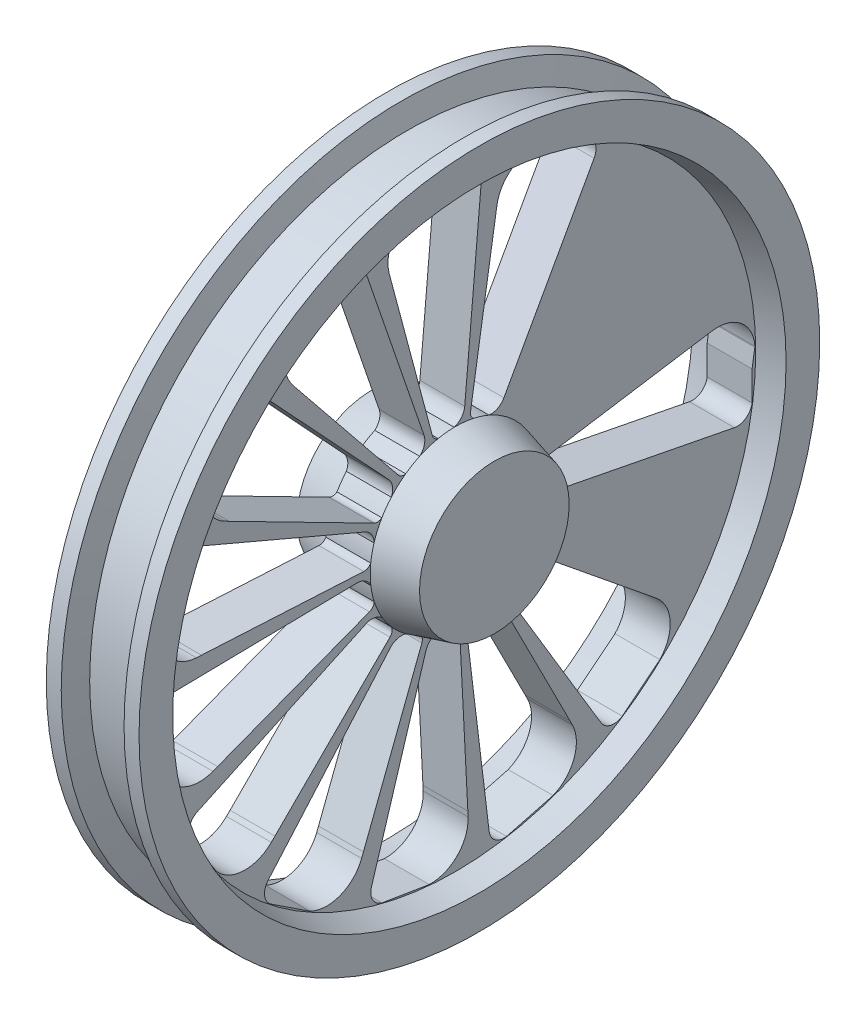
SolidWorks part; units mm, degrees
material "Alliage 1060"
ref_plane "Plan de face" through (0, 0, 0) normal (0, 0, 1) x (1, 0, 0)
ref_plane "Plan de dessus" through (0, 0, 0) normal (0, 1, 0) x (1, 0, 0)
ref_plane "Plan de droite" through (0, 0, 0) normal (1, 0, 0) x (0, 0, -1)
sketch "Esquisse1" plane through (0, 0, 0) normal (0, 0, 1) x (1, 0, 0)
  line L0 (51.1425, 233.8946) -> (71.1425, 233.8946)
  line L1 (71.1425, 233.8946) -> (79.181, 203.8946)
  line L2 (79.181, 203.8946) -> (147.1041, 203.8946)
  line L3 (147.1041, 203.8946) -> (155.1425, 233.8946)
  line L4 (155.1425, 233.8946) -> (175.1425, 233.8946)
  line L5 (175.1425, 233.8946) -> (175.1425, 188.8946)
  line L6 (175.1425, 188.8946) -> (143.1425, 180.3202)
  line L7 (143.1425, 180.3202) -> (143.1425, -107.1721)
  line L8 (143.1425, -107.1721) -> (195.1425, -121.1054)
  line L10 (195.1425, -121.1054) -> (195.1425, -221.1054)
  line L11 (195.1425, -221.1054) -> (31.1425, -221.1054)
  line L12 (31.1425, -221.1054) -> (31.1425, -121.1054)
  line L13 (31.1425, -121.1054) -> (83.1425, -107.1721)
  line L14 (83.1425, -107.1721) -> (83.1425, 180.3202)
  line L15 (83.1425, 180.3202) -> (51.1425, 188.8946)
  line L16 (51.1425, 188.8946) -> (51.1425, 233.8946)
  line L17 (31.1425, -121.1054) -> (195.1425, -121.1054) construction
  line L18 (71.1425, 233.8946) -> (71.1425, 159.3597) construction
  line L19 (155.1425, 233.8946) -> (155.1425, 155.5185)
  line L20 (51.1425, 188.8946) -> (148.536, 188.8946) construction
  line L21 (51.1425, 233.8946) -> (175.1425, 233.8946) construction
  point P23 (79.181, 203.8946)
  dimension "D1" = 60
  dimension "D2" = 100
  dimension "D3" = 15
  dimension "D4" = 455
  dimension "D5" = 15
  dimension "D6" = 15
  dimension "D7" = 15
  dimension "D8" = 164
  dimension "D9" = 45
  dimension "D10" = 45
  dimension "D11" = 30
  dimension "D12" = 20
  dimension "D13" = 124
  dimension "D14" = 15
  dimension "D15" = 15
revolve "Révolution1" add sketch "Esquisse1" angle 360 about L11 region at (111.8541, -45.1087, 0) region at (164.9552, 210.0297, 0)
sketch "Esquisse2" plane through (83.1425, 0, 0) normal (-1, 0, 0) x (0, 0, 1)
  line L0 (-117.8578, 162.629) -> (-117.8406, 162.6342)
  line L6 (-100, -221.1054) -> (100, -221.1054)
  line L7 (0, -321.1054) -> (0, -121.1054)
  line L8 (30.849, -102.3063) -> (86.824, 107.6673)
  line L9 (42.041, -96.1248) -> (122.568, 138.7163)
  line L10 (86.824, 107.6673) -> (88.551, 114.2069)
  line L11 (48.6658, 176.253) -> (48.1006, 176.35)
  line L12 (148.948, 150.7852) -> (173.1933, 141.0363)
  line L13 (52.7837, -120.8645) -> (53.3216, -121.1054)
  line L14 (19.1866, -109.5284) -> (9.6457, -107.5811)
  line L15 (19.1866, -109.5284) -> (32.7092, -111.9683)
  line L16 (32.7092, -111.9683) -> (52.7837, -120.8645)
  line L17 (48.1006, 176.35) -> (75.4732, 173.1614)
  line L18 (75.4732, 173.1614) -> (124.9878, 160.3662)
  line L19 (124.9878, 160.3662) -> (148.948, 150.7852)
  line L20 (76.5019, -125.1244) -> (213.0416, 43.9289)
  line L21 (89.2406, -124.0295) -> (258.3241, 57.7551)
  line L22 (213.0416, 43.9289) -> (217.2791, 49.2007)
  line L23 (62.9103, -126.9787) -> (74.2715, -134.7077)
  line L24 (74.2715, -134.7077) -> (88.9919, -150.9998)
  line L25 (205.6018, 122.4239) -> (229.3109, 108.3775)
  line L26 (229.3109, 108.3775) -> (269.3405, 76.5491)
  line L27 (269.3405, 76.5491) -> (287.3323, 58.0509)
  line L28 (108.927, -164.5385) -> (302.4224, -65.6363)
  line L29 (121.0096, -168.7196) -> (349.4136, -71.4235)
  line L30 (302.4224, -65.6363) -> (308.4378, -62.5439)
  line L31 (95.7562, -160.7043) -> (102.9915, -172.3861)
  line L32 (102.9915, -172.3861) -> (109.8127, -193.257)
  line L33 (327.5525, 9.0984) -> (343.4988, -13.3769)
  line L34 (343.4988, -13.3769) -> (367.1218, -58.7351)
  line L35 (367.1218, -58.7351) -> (376.0342, -82.952)
  line L36 (122.5176, -213.7336) -> (339.5116, -202.0836)
  line L37 (131.855, -222.4676) -> (380.0864, -226.4835)
  line L38 (339.5116, -202.0836) -> (346.2647, -201.7052)
  line L39 (112.045, -204.8738) -> (113.9033, -218.4885)
  line L40 (113.9033, -218.4885) -> (111.6459, -240.3295)
  line L41 (392.8664, -144.0313) -> (398.2925, -171.0495)
  line L42 (398.2925, -171.0495) -> (401.4244, -222.0946)
  line L43 (401.4244, -222.0946) -> (399.7164, -247.8428)
  line L44 (114.9238, -264.2033) -> (317.8961, -341.8199)
  line L45 (119.9015, -275.9802) -> (345.0387, -380.6136)
  line L46 (317.8961, -341.8199) -> (324.2193, -344.221)
  line L47 (108.9602, -251.8499) -> (105.1202, -265.0434)
  line L48 (105.1202, -265.0434) -> (94.1744, -284.078)
  line L49 (390.2502, -310.4879) -> (384.2179, -337.3773)
  line L50 (384.2179, -337.3773) -> (366.3171, -385.2831)
  line L51 (366.3171, -385.2831) -> (354.284, -408.1106)
  line L52 (87.4586, -307.221) -> (241.3136, -460.6836)
  line L53 (87.2159, -320.0043) -> (250.3307, -507.1633)
  line L54 (241.3136, -460.6836) -> (246.1134, -465.449)
  line L55 (87.0352, -293.51) -> (78.1609, -304.001)
  line L56 (78.1609, -304.001) -> (60.4194, -316.9379)
  line L57 (320.1561, -461.4895) -> (303.7085, -483.6005)
  line L58 (303.7085, -483.6005) -> (267.8702, -520.0838)
  line L59 (267.8702, -520.0838) -> (247.5927, -536.0434)
  line L60 (44.871, -335.3485) -> (123.0057, -538.122)
  line L61 (39.4499, -346.928) -> (112.3383, -584.2509)
  line L62 (123.0057, -538.122) -> (125.4523, -544.4277)
  line L63 (50.061, -322.6507) -> (37.6869, -328.6252)
  line L64 (37.6869, -328.6252) -> (16.2173, -333.2275)
  line L65 (194.7042, -570.9264) -> (170.6851, -584.436)
  line L66 (170.6851, -584.436) -> (123.1062, -603.1884)
  line L67 (123.1062, -603.1884) -> (98.0904, -609.5206)
  line L68 (-5.4751, -343.7224) -> (-16.571, -560.7454)
  line L69 (-15.1374, -352.0958) -> (-45.0785, -598.5475)
  line L70 (-16.571, -560.7454) -> (-16.9006, -567.5011)
  line L71 (4.4308, -334.2333) -> (-9.3036, -334.6583)
  line L72 (-9.3036, -334.6583) -> (-30.7889, -330.1302)
  line L73 (35.5861, -619.8761) -> (8.1488, -622.4483)
  line L74 (8.1488, -622.4483) -> (-42.9441, -620.2274)
  line L75 (-42.9441, -620.2274) -> (-68.3727, -615.8373)
  line L76 (-54.8746, -330.8946) -> (-153.2824, -524.642)
  line L77 (-67.1072, -334.6141) -> (-194.7007, -547.5808)
  line L78 (-153.2824, -524.642) -> (-156.3313, -530.6795)
  line L79 (-41.9655, -326.2551) -> (-54.6854, -321.057)
  line L80 (-54.6854, -321.057) -> (-72.4715, -308.1815)
  line L81 (-129.6851, -599.8748) -> (-155.7966, -591.0648)
  line L82 (-155.7966, -591.0648) -> (-201.5689, -568.2545)
  line L83 (-201.5689, -568.2545) -> (-223.0135, -553.9013)
  line L84 (-94.7857, -299.0834) -> (-263.4899, -436.0543)
  line L85 (-107.4737, -297.5058) -> (-310.6575, -440.1636)
  line L86 (-263.4899, -436.0543) -> (-268.7309, -440.3298)
  line L87 (-81.1056, -300.0955) -> (-90.6115, -290.1732)
  line L88 (-90.6115, -290.1732) -> (-101.623, -271.1766)
  line L89 (-272.5326, -514.3807) -> (-292.8033, -495.712)
  line L90 (-292.8033, -495.712) -> (-325.3406, -456.2565)
  line L91 (-325.3406, -456.2565) -> (-339.0932, -434.4218)
  line L92 (-118.3076, -253.789) -> (-328.1376, -310.3)
  line L93 (-129.2569, -247.1872) -> (-372.8987, -294.8692)
  line L94 (-328.1376, -310.3) -> (-334.6644, -312.0741)
  line L95 (-106.2218, -260.2778) -> (-110.8702, -247.347)
  line L96 (-110.8702, -247.347) -> (-113.203, -225.5139)
  line L97 (-368.2568, -378.1768) -> (-379.1817, -352.8771)
  line L98 (-379.1817, -352.8771) -> (-392.858, -303.5986)
  line L99 (-392.858, -303.5986) -> (-396.5407, -278.058)
  line L100 (-121.3729, -202.8433) -> (-336.0473, -169.1231)
  line L101 (-128.6905, -192.3587) -> (-370.6624, -136.8204)
  line L102 (-336.0473, -169.1231) -> (-342.7315, -168.0892)
  line L103 (-112.9713, -213.6868) -> (-111.9583, -199.9833)
  line L104 (-111.9583, -199.9833) -> (-105.2092, -179.0889)
  line L105 (-400.306, -214.8137) -> (-399.9961, -187.2578)
  line L106 (-399.9961, -187.2578) -> (-392.4466, -136.677)
  line L107 (-392.4466, -136.677) -> (-385.4226, -111.8466)
  line L108 (-103.4518, -155.0553) -> (-285.8514, -36.9345)
  line L109 (-105.8723, -142.5009) -> (-304.3352, 6.6547)
  line L110 (-285.8514, -36.9345) -> (-291.5372, -33.2712)
  line L111 (-100.187, -168.3786) -> (-93.6879, -156.2718)
  line L112 (-93.6879, -156.2718) -> (-79.0238, -139.929)
  line L113 (-363.1386, -52.5386) -> (-351.6475, -27.491)
  line L114 (-351.6475, -27.491) -> (-324.1777, 15.6462)
  line L115 (-324.1777, 15.6462) -> (-307.6615, 35.473)
  line L116 (-67.643, -118.688) -> (-186.2292, 63.4093)
  line L117 (-64.7478, -106.2345) -> (-185.3856, 110.7481)
  line L118 (-186.2292, 63.4093) -> (-189.9334, 69.0685)
  line L119 (-70.0795, -132.1874) -> (-59.2179, -123.7707)
  line L120 (-59.2179, -123.7707) -> (-39.1744, -114.8052)
  line L121 (-263.1813, 80.5899) -> (-242.4959, 98.7981)
  line L122 (-242.4959, 98.7981) -> (-199.8555, 127.0329)
  line L123 (-199.8555, 127.0329) -> (-176.7029, 138.4279)
  line L124 (-20.138, -100.0296) -> (-54.4063, 114.558)
  line L125 (-12.4278, -89.8303) -> (-34.3812, 157.461)
  line L126 (-54.4063, 114.558) -> (-55.4884, 121.2345)
  line L127 (-27.8546, -111.3708) -> (-14.5087, -108.0996)
  line L128 (-14.5087, -108.0996) -> (7.4486, -108.0617)
  line L129 (-117.7176, 161.5524) -> (-91.4146, 169.773)
  line L130 (-91.4146, 169.773) -> (-40.9765, 178.2233)
  line L131 (-40.9765, 178.2233) -> (-15.1908, 179.2161)
  line L132 (-176.7029, 138.4279) -> (-117.8406, 162.6342)
  line L133 (48.6658, 176.253) -> (-15.1908, 179.2161)
  line L134 (173.1933, 141.0363) -> (206.0786, 122.1054)
  line L135 (287.3323, 58.0509) -> (327.5525, 9.0984)
  line L136 (376.0342, -82.952) -> (392.8664, -144.0313)
  line L137 (399.7164, -247.8428) -> (390.2502, -310.4879)
  line L138 (324.2193, -457.8001) -> (327.2503, -453.5915)
  line L139 (-131.1673, -599.3747) -> (-68.3727, -615.8373)
  line L140 (-273.9608, -513.0655) -> (-223.0135, -553.9013)
  line L141 (-368.2568, -378.1768) -> (-339.0932, -434.4218)
  line L142 (-400.2686, -214.2415) -> (-396.5407, -278.058)
  line L143 (-363.1386, -52.5386) -> (-385.4226, -111.8466)
  line L144 (-263.1813, 80.5899) -> (-307.6615, 35.473)
  line L145 (-117.7176, 161.5524) -> (-176.7029, 138.4279)
  line L146 (48.6658, 176.253) -> (-15.1908, 179.2161)
  line L147 (287.4774, 57.8744) -> (327.8586, 8.6135)
  line L148 (376.0342, -82.952) -> (392.9488, -144.5989)
  line L149 (399.7164, -247.8428) -> (390.0946, -311.0399)
  line L150 (354.284, -408.1106) -> (319.7895, -461.9304)
  line L151 (247.5927, -536.0434) -> (194.1899, -571.1801)
  line L152 (35.5861, -619.8761) -> (98.0904, -609.5206)
  line L153 (-129.6851, -599.8748) -> (-70.0795, -615.3899)
  line L154 (-272.5326, -514.3807) -> (-223.0135, -553.9013)
  line L155 (-366.9932, -380.6136) -> (-339.0932, -434.4218)
  line L156 (35.5861, -619.8761) -> (98.0904, -609.5206)
  line L157 (-368.2568, -378.1768) -> (-339.0932, -434.4218)
  line L158 (-363.1386, -52.5386) -> (-385.4226, -111.8466)
  line L159 (-263.1813, 80.5899) -> (-307.6615, 35.473)
  line L160 (-117.1618, 161.6937) -> (-176.7029, 138.4279)
  line L161 (35.0131, -619.8987) -> (98.0904, -609.5206)
  line L162 (-106.2218, -260.2778) -> (-101.623, -271.1766)
  line L163 (-100.187, -168.3786) -> (-105.2092, -179.0889)
  line L164 (-70.0795, -132.1874) -> (-79.0238, -139.929)
  line L165 (-363.1386, -52.5386) -> (-385.4226, -111.8466)
  line L166 (-100.187, -168.2673) -> (-103.1615, -172.9523)
  line L167 (-103.1615, -172.9523) -> (-105.2092, -179.0889)
  line L168 (-363.1386, -52.5386) -> (-372.8987, -82.4119)
  line L169 (-372.8987, -82.4119) -> (-385.5567, -112.3204)
  line L170 (-307.6615, 35.473) -> (-282.8766, 62.4734)
  line L171 (-282.8766, 62.4734) -> (-263.1813, 80.5899)
  line L172 (-282.8766, 62.0557) -> (-282.8766, 62.4734)
  line L173 (-282.8766, 62.4734) -> (-307.6615, 35.473)
  line L174 (-282.8766, 62.0557) -> (-307.6615, 35.473)
  line L175 (-307.6615, 35.473) -> (-292.0889, 53.417)
  line L176 (-292.0889, 53.417) -> (-282.8766, 61.8307)
  line L177 (-282.8766, 61.8307) -> (-282.8766, 62.0557)
  line L178 (-106.2218, -260.2778) -> (-101.5238, -271.3479)
  line L179 (-106.2218, -260.2778) -> (-106.2218, -265.0434)
  line L180 (-106.2218, -265.0434) -> (-101.3705, -271.6122)
  line L181 (-338.8163, -434.8616) -> (-348.7383, -402.6142)
  line L182 (-348.7383, -402.6142) -> (-368.2568, -378.1768)
  line L183 (-396.5407, -278.058) -> (-396.5407, -238.7218)
  line L184 (-396.5407, -238.7218) -> (-400.306, -214.8137)
  line L185 (-112.9713, -213.6868) -> (-114.4986, -218.4885)
  line L186 (-114.4986, -218.4885) -> (-113.203, -225.5139)
  line L187 (-100.187, -168.3786) -> (-105.5618, -176.6782)
  line L188 (-105.5618, -176.6782) -> (-105.2939, -179.342)
  line L189 (-307.6615, 35.473) -> (-266.5954, 74.2264)
  line L190 (-266.5954, 74.2264) -> (-263.4168, 80.351)
  line L191 (-70.0795, -132.1874) -> (-78.7587, -136.8204)
  line L192 (-78.7587, -136.8204) -> (-79.3723, -139.6632)
  circle A0 centre (0, -221.1054) radius 401.4256 construction
  circle A1 centre (0, -221.1054) radius 113.9334 construction
  circle A6 centre (0, -221.1054) radius 100 construction
  arc A7 (48.6658, 176.253) -> (88.551, 114.2069) centre (40.2083, 126.9734) cw
  arc A8 (148.948, 150.7852) -> (122.568, 138.7163) centre (141.4867, 132.2291) ccw
  arc A9 (52.7837, -120.8645) -> (42.041, -96.1248) centre (60.9597, -102.612) cw
  arc A10 (30.849, -102.3063) -> (19.1866, -109.5284) centre (21.1864, -99.7304) cw
  arc A11 (88.9919, -150.9998) -> (89.2406, -124.0295) centre (103.8851, -137.6508) cw
  arc A12 (76.5019, -125.1244) -> (62.9103, -126.9787) centre (68.7224, -118.8411) cw
  arc A13 (206.0786, 122.1054) -> (217.2791, 49.2007) centre (178.3086, 80.5262) cw
  arc A14 (287.3323, 58.0509) -> (258.3241, 57.7551) centre (272.9686, 44.1339) ccw
  arc A15 (109.8127, -193.257) -> (121.0096, -168.7196) centre (128.8478, -187.1197) cw
  arc A16 (108.927, -164.5385) -> (95.7562, -160.7043) centre (104.3757, -155.6343) cw
  arc A17 (327.8586, 8.6135) -> (308.4378, -62.5439) centre (285.5776, -18.0758) cw
  arc A18 (376.0342, -82.952) -> (349.4136, -71.4235) centre (357.2518, -89.8236) ccw
  arc A19 (111.6459, -240.3295) -> (131.855, -222.4676) centre (131.5315, -242.465) cw
  arc A20 (122.5176, -213.7336) -> (112.045, -204.8738) centre (121.9815, -203.748) cw
  arc A21 (392.9488, -144.5989) -> (346.2647, -201.7052) centre (343.4677, -151.7835) cw
  arc A22 (399.7164, -247.8428) -> (380.0864, -226.4835) centre (379.7628, -246.4809) ccw
  arc A23 (94.1744, -284.078) -> (119.9015, -275.9802) centre (111.4723, -294.1171) cw
  arc A24 (114.9238, -264.2033) -> (108.9602, -251.8499) centre (118.4955, -254.8629) cw
  arc A25 (390.0946, -311.0399) -> (324.2193, -344.221) centre (341.9691, -297.4776) cw
  arc A26 (354.284, -408.1106) -> (345.0387, -380.6136) centre (336.6095, -398.7505) ccw
  arc A27 (60.4194, -316.9379) -> (87.2159, -320.0043) centre (72.1385, -333.1448) cw
  arc A28 (87.4586, -307.221) -> (87.0352, -293.51) centre (94.5206, -300.1409) cw
  arc A29 (319.7895, -461.9304) -> (246.1134, -465.449) centre (281.341, -429.9663) cw
  arc A30 (247.5927, -536.0434) -> (250.3307, -507.1633) centre (235.2533, -520.3037) ccw
  arc A31 (16.2173, -333.2275) -> (39.4499, -346.928) centre (20.3313, -352.7998) cw
  arc A32 (44.871, -335.3485) -> (50.061, -322.6507) centre (54.2022, -331.7529) cw
  arc A33 (194.1899, -571.1801) -> (125.4523, -544.4277) centre (172.0664, -526.341) cw
  arc A34 (98.0904, -609.5206) -> (112.3383, -584.2509) centre (93.2197, -590.1228) ccw
  arc A35 (-30.7889, -330.1302) -> (-15.1374, -352.0958) centre (-34.9914, -349.6837) cw
  arc A36 (-5.4751, -343.7224) -> (4.4308, -334.2333) centre (4.5118, -344.233) cw
  arc A37 (35.0131, -619.8987) -> (-16.9006, -567.5011) centre (33.04, -569.9377) cw
  arc A38 (-68.3727, -615.8373) -> (-45.0785, -598.5475) centre (-64.9325, -596.1354) ccw
  arc A39 (-72.4715, -308.1815) -> (-67.1072, -334.6141) centre (-84.2637, -324.3353) cw
  arc A40 (-54.8746, -330.8946) -> (-41.9655, -326.2551) centre (-45.9587, -335.4232) cw
  arc A41 (-130.2178, -599.6624) -> (-156.3313, -530.6795) centre (-111.6993, -553.2181) cw
  arc A42 (-223.0135, -553.9013) -> (-194.7007, -547.5808) centre (-211.8572, -537.3019) ccw
  arc A43 (-101.623, -271.1766) -> (-107.4737, -297.5058) centre (-118.9661, -281.1374) cw
  arc A44 (-94.7857, -299.0834) -> (-81.1056, -300.0955) centre (-88.4826, -306.8468) cw
  arc A45 (-272.9329, -513.9701) -> (-268.7309, -440.3298) centre (-237.1248, -479.0733) cw
  arc A46 (-339.0932, -434.4218) -> (-310.6575, -440.1636) centre (-322.1499, -423.7952) ccw
  arc A47 (-113.203, -225.5139) -> (-129.2569, -247.1872) centre (-133.0982, -227.5595) cw
  arc A48 (-118.3076, -253.789) -> (-106.2218, -260.2778) centre (-115.7071, -263.4449) cw
  arc A49 (-368.4553, -377.6388) -> (-334.6644, -312.0741) centre (-321.5493, -360.3234) cw
  arc A50 (-396.5407, -278.058) -> (-372.8987, -294.8692) centre (-376.74, -275.2416) ccw
  arc A51 (-105.2092, -179.0889) -> (-128.6905, -192.3587) centre (-124.2163, -172.8656) cw
  arc A52 (-121.3729, -202.8433) -> (-112.9713, -213.6868) centre (-122.9247, -212.7222) cw
  arc A53 (-400.2686, -214.2415) -> (-342.7315, -168.0892) centre (-350.375, -217.5015) cw
  arc A54 (-385.4226, -111.8466) -> (-370.6624, -136.8204) centre (-366.1883, -117.3273) ccw
  arc A55 (-79.0238, -139.929) -> (-105.8723, -142.5009) centre (-93.8564, -126.5128) cw
  arc A56 (-103.4518, -155.0553) -> (-100.187, -168.3786) centre (-108.8875, -163.449) cw
  arc A57 (-362.8717, -52.031) -> (-291.5372, -33.2712) centre (-318.6176, -75.3027) cw
  arc A58 (-307.6615, 35.473) -> (-304.3352, 6.6547) centre (-292.3193, 22.6428) ccw
  arc A59 (-39.1744, -114.8052) -> (-64.7478, -106.2345) centre (-47.2678, -96.516) cw
  arc A60 (-67.643, -118.688) -> (-70.0795, -132.1874) centre (-76.0227, -124.1451) cw
  arc A61 (-262.731, 80.945) -> (-189.9334, 69.0685) centre (-231.7684, 41.6854) cw
  arc A62 (-176.7029, 138.4279) -> (-185.3856, 110.7481) centre (-167.9056, 120.4666) ccw
  arc A63 (7.4486, -108.0617) -> (-12.4278, -89.8303) centre (7.4938, -88.0617) cw
  arc A64 (-20.138, -100.0296) -> (-27.8546, -111.3708) centre (-30.0129, -101.6065) cw
  arc A65 (-117.1618, 161.6937) -> (-55.4884, 121.2345) centre (-104.8443, 113.2346) cw
  arc A66 (-15.1908, 179.2161) -> (-34.3812, 157.461) centre (-14.4596, 159.2295) ccw
  circle A67 centre (0, -221.1054) radius 455 construction
  circle A68 centre (0, -221.1054) radius 401.4256
  circle A70 centre (0, -221.1054) radius 113.9334
  circle A71 centre (0, -221.1054) radius 113.9334
  point P10 (102.4967, 167.0144)
  point P11 (12.9028, 180.1128)
  point P12 (-36.3379, 178.6721)
  point P19 (-3.0907, -107.214)
  point P27 (0, -221.1054)
  point P279 (0, -221.1054)
  circle M12 centre (0, -221.1054) radius 113.9334
  dimension "D1" = 50
  dimension "D2" = 20
  dimension "D3" = 20
  dimension "D4" = 10
  dimension "D5" = 4
  dimension "D7" = 0
  dimension "D6" = 15
extrude "Enlèv. mat.-Extru.2" cut sketch "Esquisse2" against normal through all contours A53 L142 L99 A50 L93 A47 A52 L100 L102 M12 | A45 L140 L83 A42 L77 A39 A44 L84 L86 M12 | A41 L139 L75 A38 L69 A35 A40 L76 L78 M12 | A33 L151 L59 A30 L53 A27 A32 L60 L62 M12 | A29 L150 L51 A26 L45 A23 A28 L52 L54 M12 | A25 L149 L43 A22 L37 A19 A24 L44 L46 M12 | A21 L148 L35 A18 L29 A15 A20 L36 L38 M12 | A17 L147 L135 L27 A14 L21 A11 A16 L28 L30 M12 | A13 L134 L12 L19 A8 L9 A9 A12 L20 L22 M12 | L131 A66 L125 A63 A10 L8 L10 A7 L133 M12 | A37 L161 L67 A34 L61 A31 A36 L68 L70 M12 | A65 L160 L123 A62 L117 A59 A64 L124 L126 M12 region at (83.1425, 42.35, -93.1668) region at (83.1425, 57.4674, 22.0449) region at (83.1425, 24.7327, 133.5633) region at (83.1425, -228.2548, -279.0175) region at (83.1425, -51.0863, 221.7709) region at (83.1425, -433.5103, -181.5696) region at (83.1425, -155.9876, 271.7507) region at (83.1425, -272.1483, 274.7425) region at (83.1425, -489.0017, -79.4802) region at (83.1425, -379.4833, 230.2287) region at (83.1425, -498.1741, 36.3554) region at (83.1425, -459.4332, 145.9063)
equation "\"A\"= 124"
equation "\"B\"= 910"
